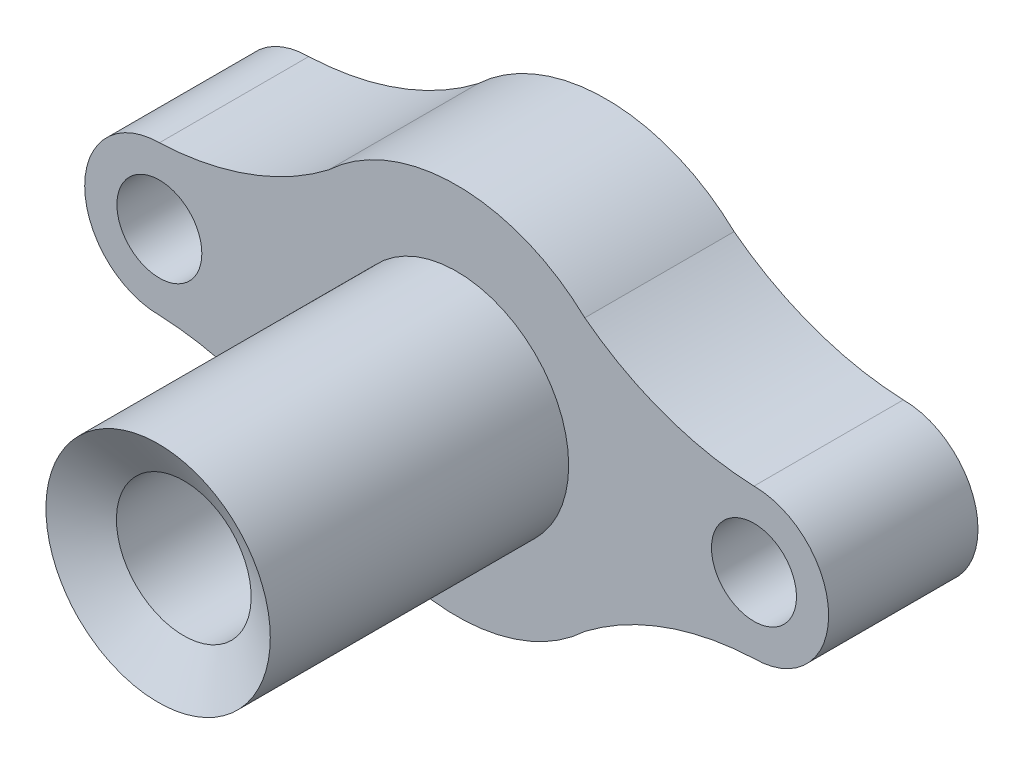
SolidWorks part; units mm, degrees
ref_plane "Front Plane" through (0, 0, 0) normal (0, 0, 1) x (1, 0, 0)
ref_plane "Top Plane" through (0, 0, 0) normal (0, 1, 0) x (1, 0, 0)
ref_plane "Right Plane" through (0, 0, 0) normal (1, 0, 0) x (0, 0, -1)
sketch "Sketch1" plane through (0, 0, 0) normal (0, 0, 1) x (1, 0, 0)
  line L0 (-199.055, 0) -> (0, 0) construction
  line L1 (0, 162.3079) -> (0, -190.4986) construction
  arc A0 (-85.7819, -90.9201) -> (85.7819, -90.9201) centre (0, 0) ccw
  arc A1 (-199.055, 50) -> (-199.055, -50) centre (-199.055, 0) ccw
  arc A2 (-199.055, 50) -> (-85.7819, 90.9201) centre (-207.2174, 249.8334) ccw
  arc A3 (-199.055, -50) -> (-85.7819, -90.9201) centre (-207.2174, -249.8334) cw
  arc A4 (199.055, -50) -> (85.7819, -90.9201) centre (207.2174, -249.8334) ccw
  arc A5 (199.055, 50) -> (199.055, -50) centre (199.055, 0) cw
  arc A6 (199.055, 50) -> (85.7819, 90.9201) centre (207.2174, 249.8334) cw
  arc A7 (85.7819, 90.9201) -> (-85.7819, 90.9201) centre (0, 0) ccw
  circle A8 centre (-199.055, 0) radius 28.4398
  circle A9 centre (199.055, 0) radius 28.4398
  dimension "D1" = 250
  dimension "D2" = 100
  dimension "D3" = 200
extrude "Boss-Extrude1" add sketch "Sketch1" along normal blind 100
sketch "Sketch2" plane through (0, 0, 100) normal (0, 0, 1) x (1, 0, 0)
  circle A0 centre (0, 0) radius 75
  dimension "D1" = 150
extrude "Boss-Extrude2" add sketch "Sketch2" along normal blind 200 separate body
shell "Shell2" thickness 30 removed face at (75, 0, 300)
combine bodies "Combine1" operation type add bodies to combine 102 101
sketch "Sketch4" plane through (0, 0, 0) normal (0, 1, 0) x (1, 0, 0)
  line L0 (0.1831, -256.9008) -> (-75, -300)
  line L1 (-75, -300) -> (0.1831, -300)
  line L2 (0.1831, -300) -> (0.1831, -256.9008)
  point P2 (-71.29, -299.855)
  point P4 (0, 0)
  point P5 (-75, -300)
revolve "Cut-Revolve1" cut sketch "Sketch4" angle 360 about L2
